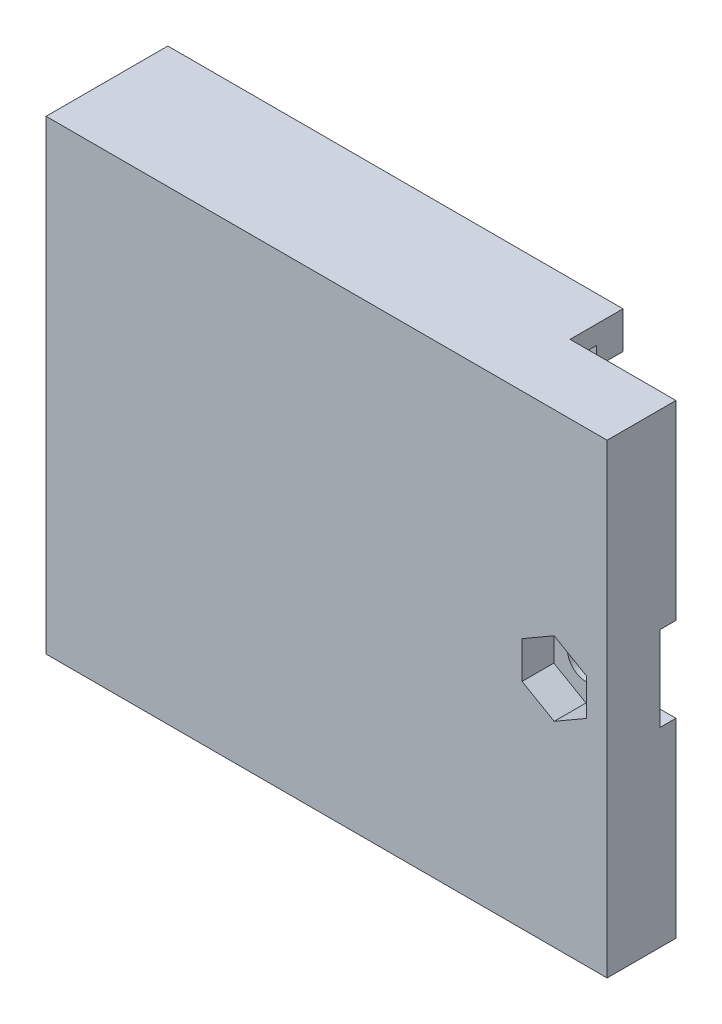
SolidWorks part; units mm, degrees
ref_plane "Alzado" through (0, 0, 0) normal (0, 0, 1) x (1, 0, 0)
ref_plane "Planta" through (0, 0, 0) normal (0, 1, 0) x (1, 0, 0)
ref_plane "Vista lateral" through (0, 0, 0) normal (1, 0, 0) x (0, 0, -1)
sketch "Croquis1" plane through (0, 0, 0) normal (0, 0, 1) x (1, 0, 0)
  line L1 (-26.5, 22) -> (26.5, 22)
  line L2 (-26.5, 22) -> (-26.5, -22)
  line L3 (-26.5, -22) -> (26.5, -22)
  line L4 (26.5, 22) -> (26.5, -22)
  line L5 (-26.5, 22) -> (26.5, -22) construction
  line L6 (-26.5, -22) -> (26.5, 22) construction
  circle A0 centre (21.5, 0) radius 1.75
  point P0 (0, 0)
  dimension "D4" = 3.5
  dimension "D1" = 44
  dimension "D2" = 53
  dimension "D3" = 5
extrude "Saliente-Extruir1" add sketch "Croquis1" along normal blind 6.5
sketch "Croquis3" plane through (0, 0, 0) normal (0, 0, -1) x (-1, 0, 0)
  line L0 (-16.5, -22) -> (-16.5, -20.25)
  line L1 (26.5, -22) -> (-26.5, -22) construction
  line L2 (-16.5, -20.25) -> (26.5, -20.25)
  line L3 (26.5, 22) -> (26.5, -22) construction
  line L4 (26.5, -20.25) -> (26.5, -22)
  line L5 (26.5, -22) -> (-16.5, -22)
  line L6 (-26.5, -22) -> (-26.5, 22) construction
  line L7 (26.5, 22) -> (-16.5, 22)
  line L8 (-26.5, 22) -> (26.5, 22) construction
  line L9 (-16.5, 22) -> (-16.5, 20.25)
  line L10 (-16.5, 20.25) -> (26.5, 20.25)
  line L11 (26.5, 20.25) -> (26.5, 22)
  dimension "D1" = 10
  dimension "D2" = 1.75
extrude "Saliente-Extruir2" add sketch "Croquis3" along normal blind 5
sketch "Croquis4" plane through (0, 0, -5) normal (0, 0, -1) x (-1, 0, 0)
  line L0 (-16.5, -20.25) -> (26.5, -20.25)
  line L1 (26.5, -20.25) -> (26.5, -18.5)
  line L2 (26.5, 20.25) -> (26.5, -20.25) construction
  line L3 (26.5, -18.5) -> (-16.5, -18.5)
  line L4 (-16.5, -18.5) -> (-16.5, -20.25)
  line L5 (-16.5, 20.25) -> (-16.5, 18.5)
  line L6 (-16.5, 18.5) -> (26.5, 18.5)
  line L7 (26.5, 18.5) -> (26.5, 20.25)
  line L8 (26.5, 20.25) -> (-16.5, 20.25)
  dimension "D1" = 1.75
  dimension "D2" = 1.75
extrude "Saliente-Extruir3" add sketch "Croquis4" against normal blind 2.5
sketch "Croquis5" plane through (0, 0, 0) normal (0, 0, -1) x (-1, 0, 0)
  line L0 (26.5, -4) -> (26.5, 4)
  line L1 (26.5, 20.25) -> (26.5, -20.25) construction
  line L2 (26.5, -4) -> (-26.5, -4)
  line L3 (-26.5, -4) -> (-26.5, 4)
  line L4 (-26.5, 4) -> (26.5, 4)
  point P4 (26.5, 0)
  dimension "D1" = 8
  dimension "D2" = 53
extrude "Cortar-Extruir2" cut sketch "Croquis5" against normal blind 1.5
sketch "Croquis8" plane through (0, 0, 1.5) normal (0, 0, -1) x (-1, 0, 0)
  line L0 (26.5, -4) -> (26.5, 4)
  line L1 (26.5, 4) -> (25, 4)
  line L2 (26.5, 4) -> (-26.5, 4) construction
  line L3 (25, 4) -> (25, -4)
  line L4 (-26.5, -4) -> (26.5, -4) construction
  line L5 (25, -4) -> (26.5, -4)
  dimension "D1" = 1.5
extrude "Saliente-Extruir6" add sketch "Croquis8" along normal blind 3
sketch "Croquis10" plane through (0, 0, 6.5) normal (0, 0, 1) x (1, 0, 0)
  line L1 (21.5, -3.5) -> (24.5311, -1.75)
  line L2 (24.5311, -1.75) -> (24.5311, 1.75)
  line L3 (24.5311, 1.75) -> (21.5, 3.5)
  line L4 (21.5, 3.5) -> (18.4689, 1.75)
  line L5 (18.4689, 1.75) -> (18.4689, -1.75)
  line L6 (18.4689, -1.75) -> (21.5, -3.5)
  circle A0 centre (21.5, 0) radius 3.0311 construction
  dimension "D1" = 7
extrude "Cortar-Extruir3" cut sketch "Croquis10" against normal blind 3
sketch "Croquis11" plane through (0, 0, 1.5) normal (0, 0, -1) x (-1, 0, 0)
  line L0 (25, -4) -> (-2, -4)
  line L1 (-26.5, -4) -> (25, -4) construction
  line L2 (-2, -4) -> (-2, 4)
  line L3 (25, 4) -> (-26.5, 4) construction
  line L4 (-2, 4) -> (25, 4)
  line L5 (25, 4) -> (25, -4)
  dimension "D1" = 27
extrude "Saliente-Extruir7" add sketch "Croquis11" along normal blind 2.6
sketch "Croquis12" plane through (0, 0, 0) normal (0, 0, -1) x (-1, 0, 0)
  line L0 (25, -4) -> (25, -18.5)
  line L1 (26.5, -18.5) -> (-16.5, -18.5) construction
  line L2 (25, -18.5) -> (-16.5, -18.5)
  line L3 (-16.5, -18.5) -> (-16.5, -4)
  line L4 (-26.5, -4) -> (-2, -4) construction
  line L5 (-16.5, -4) -> (25, -4)
  line L6 (25, 4) -> (25, 18.5)
  line L7 (-16.5, 18.5) -> (26.5, 18.5) construction
  line L8 (25, 18.5) -> (-16.5, 18.5)
  line L9 (-16.5, 18.5) -> (-16.5, 4)
  line L10 (-2, 4) -> (-26.5, 4) construction
  line L11 (-16.5, 4) -> (25, 4)
extrude "Cortar-Extruir4" cut sketch "Croquis12" against normal up to surface (1.5 mm away) up to face at (23.25, 0, 1.5)
